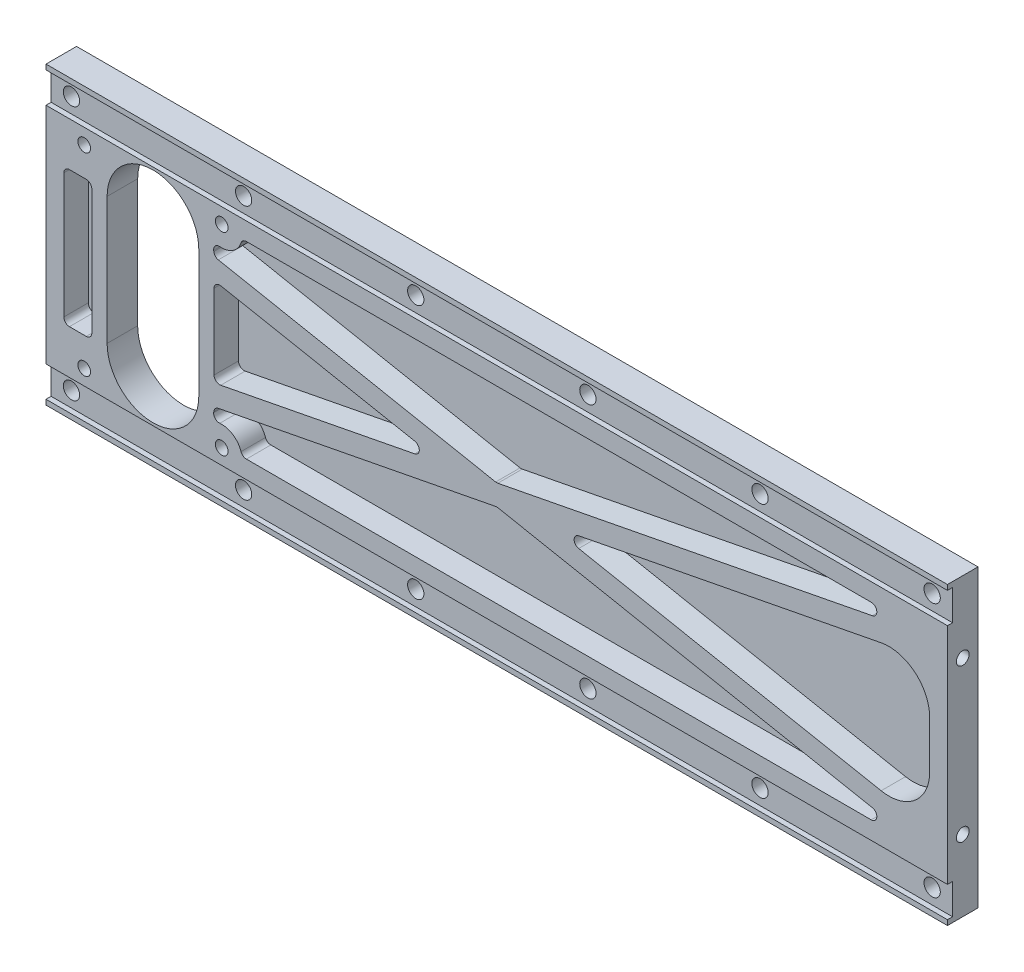
SolidWorks part; units mm, degrees
material "3.1325 (EN-AW 2017A)"
ref_plane "正面" through (0, 0, 0) normal (0, 0, 1) x (1, 0, 0)
ref_plane "平面" through (0, 0, 0) normal (0, 1, 0) x (1, 0, 0)
ref_plane "右側面" through (0, 0, 0) normal (1, 0, 0) x (0, 0, -1)
sketch "ｽｹｯﾁ1" plane through (0, 0, 0) normal (0, 0, 1) x (1, 0, 0)
  line L0 (0, 0) -> (27261.2982, 0) construction
  line L1 (0, 0) -> (0, 22) construction
  line L2 (-88.5, -29) -> (88.5, -29)
  line L3 (-88.5, -29) -> (-88.5, 29)
  line L4 (-88.5, 29) -> (88.5, 29)
  line L5 (88.5, -29) -> (88.5, 29)
  line L6 (-88.5, 28) -> (88.5, 28)
  line L7 (88.5, 22) -> (-88.5, 22)
  line L8 (-88.5, 25) -> (88.5, 25) construction
  line L9 (0, 22) -> (0, 28) construction
  line L10 (0, 28) -> (0, 29) construction
  line L11 (-88.5, -28) -> (88.5, -28)
  line L12 (88.5, -22) -> (-88.5, -22)
  line L13 (-58.5, 12.5) -> (-58.5, -12.5)
  line L14 (-76.5, -12.5) -> (-76.5, 12.5)
  line L15 (-67.5, 12.5) -> (-67.5, -12.5) construction
  arc A0 (-58.5, 12.5) -> (-76.5, 12.5) centre (-67.5, 12.5) ccw
  arc A1 (-76.5, -12.5) -> (-58.5, -12.5) centre (-67.5, -12.5) ccw
  point P9 (0, 29)
  point P10 (-88.5, 0)
  point P18 (0, 25)
  point P24 (-84.5, 25)
  point P25 (0, 15)
  point P26 (-50.7, 25)
  point P27 (-16.9, 25)
  point P28 (16.9, 25)
  point P29 (50.7, 25)
  point P30 (84.5, 25)
  point P31 (0, -15)
  point P32 (84.5, -25)
  point P33 (50.7, -25)
  point P34 (16.9, -25)
  point P35 (-16.9, -25)
  point P36 (-50.7, -25)
  point P37 (-84.5, -25)
  point P38 (-81, 19)
  point P39 (-54, 19)
  point P40 (-81, -19)
  point P41 (-54, -19)
  point P43 (-67.5, 0)
  dimension "D10" = 18
  dimension "D11" = 25
  dimension "D1" = 1
  dimension "D2" = 6
  dimension "D3" = 177
  dimension "D4" = 58
  dimension "D6" = 4
  dimension "D7" = 30
  dimension "D8" = 38
  dimension "D9" = 27
  dimension "D12" = 21
  dimension "D5" = 6
extrude "ﾎﾞｽ - 押し出し1" add sketch "ｽｹｯﾁ1" along normal mid plane 6 contours L4 L5 L2 L3
extrude "ｶｯﾄ - 押し出し1" cut sketch "ｽｹｯﾁ1<3>" against normal blind 1 from surface contours L5 L12 L3 L11 | L7 L5 L6 L3 region at (0, -25, 0) region at (0, 25, 0) starting at face at (0, 0, 3)
sketch "ｽｹｯﾁ1<3>" plane through (0, 0, 0) normal (0, 0, 1) x (1, 0, 0) same geometry as "ｽｹｯﾁ1"
extrude "ｶｯﾄ - 押し出し2" cut sketch "ｽｹｯﾁ1<4>" along normal through all both and the other way through all contours L14 A0 L13 A1
sketch "ｽｹｯﾁ1<4>" plane through (0, 0, 0) normal (0, 0, 1) x (1, 0, 0) same geometry as "ｽｹｯﾁ1"
hole_wizard "M3 すきま穴1" positions "3Dｽｹｯﾁ2" profile "ｽｹｯﾁ3" hole size "M3" standard "JIS" end condition through all
sketch3d "3Dｽｹｯﾁ2"
  point P0 (-84.5, -25, -3)
  point P2 (-50.7, -25, -3)
  point P4 (-16.9, -25, -3)
  point P6 (16.9, -25, -3)
  point P8 (50.7, -25, -3)
  point P10 (84.5, -25, -3)
  point P12 (84.5, 25, -3)
  point P14 (50.7, 25, -3)
  point P16 (16.9, 25, -3)
  point P18 (-16.9, 25, -3)
  point P20 (-50.7, 25, -3)
  point P22 (-84.5, 25, -3)
sketch "ｽｹｯﾁ3" plane through (-84.5, -25, -3) normal (1, 0, 0) x (0, 1, 0)
  line L0 (0, 0) -> (0, 6)
  line L1 (0, 6) -> (1.6, 6)
  line L2 (1.6, 6) -> (1.6, 0)
  line L5 (1.6, 0) -> (0, 0)
  line L11 (0, -6.35) -> (0, 107.95) construction
  dimension "通し穴の直径" = 3.2
  dimension "通し穴の深さ" = 6
hole_wizard "M3x0.5 ねじ穴2" positions "3Dｽｹｯﾁ4" profile "ｽｹｯﾁ5" tap size "M3x0.5" standard "JIS" end condition through all
sketch3d "3Dｽｹｯﾁ4"
  point P0 (-81, 19, 3)
  point P2 (-54, 19, -3)
  point P4 (-81, -19, 3)
  point P6 (-54, -19, 3)
sketch "ｽｹｯﾁ5" plane through (-81, 19, 3) normal (1, 0, 0) x (0, -1, 0)
  line L0 (0, 0) -> (0, 6)
  line L1 (0, 6) -> (1.25, 6)
  line L2 (1.25, 6) -> (1.25, 0)
  line L5 (1.25, 0) -> (0, 0)
  line L11 (0, -6.35) -> (0, 107.95) construction
  dimension "ねじ山の主要直径" = 2.5
  dimension "次ｻｰﾌｪｽまでのねじ下穴ﾄﾞﾘﾙの深さ" = 6
sketch "ｽｹｯﾁ6" [suppressed] plane through (0, 0, 2) normal (0, 0, 1) x (1, 0, 0)
  line L0 (-88.5, 25) -> (88.5, 25) construction
  line L1 (0, 28) -> (0, 22) construction
  line L2 (12.0135, 0) -> (0, 0) construction
  line L3 (88.5, -24.1) -> (88.5, -25.9)
  line L4 (88.5, 28) -> (-88.5, 28)
  line L5 (-88.5, 28) -> (-88.5, 22)
  line L6 (-88.5, 22) -> (88.5, 22)
  line L7 (88.5, 22) -> (88.5, 28)
  line L8 (88.5, 28) -> (-88.5, 28)
  line L9 (-88.5, 25.9) -> (-88.5, 24.1)
  line L10 (-88.5, 22) -> (88.5, 22)
  line L11 (88.5, 24.1) -> (88.5, 25.9)
  line L12 (-88.5, -22) -> (88.5, -22)
  line L13 (-88.5, -25.9) -> (-88.5, -24.1)
  line L14 (88.5, -28) -> (-88.5, -28)
  arc A0 (-88.5, 28) -> (-88.5, 25.9) centre (-88.5, 26.95) ccw
  arc A1 (-88.5, 22) -> (-88.5, 24.1) centre (-88.5, 23.05) cw
  arc A2 (88.5, 22) -> (88.5, 24.1) centre (88.5, 23.05) ccw
  arc A3 (88.5, 28) -> (88.5, 25.9) centre (88.5, 26.95) cw
  arc A4 (88.5, -28) -> (88.5, -25.9) centre (88.5, -26.95) ccw
  arc A5 (88.5, -22) -> (88.5, -24.1) centre (88.5, -23.05) cw
  arc A6 (-88.5, -22) -> (-88.5, -24.1) centre (-88.5, -23.05) ccw
  arc A7 (-88.5, -28) -> (-88.5, -25.9) centre (-88.5, -26.95) cw
  dimension "D2" = 2.1
  dimension "D1" = 0
sketch "ｽｹｯﾁ7" plane through (0, 0, 3) normal (0, 0, 1) x (1, 0, 0)
  line L4 (86.2083, 16.6969) -> (-86.2083, -16.6969) construction
  line L5 (-87.6293, 16.9721) -> (87.6293, -16.9721) construction
  line L8 (85, 18.5) -> (-85, 18.5)
  line L9 (-85, 18.5) -> (-85, -18.5)
  line L10 (-85, -18.5) -> (85, -18.5)
  line L11 (85, -18.5) -> (85, 18.5)
  line L12 (85, 18.5) -> (-85, 18.5)
  line L13 (-85, 18.5) -> (-85, -18.5)
  line L14 (-85, -18.5) -> (85, -18.5)
  line L15 (85, -18.5) -> (85, 18.5)
  line L18 (-88.0096, 15.0086) -> (87.249, -18.9356)
  line L19 (86.7191, 18.833) -> (-87.5988, -14.929)
  line L20 (-85, 18.5) -> (88.0096, -15.0086)
  line L21 (87.4525, 14.9007) -> (-85, -18.5)
  line L22 (87.0994, 16.8694) -> (-87.2185, -16.8925) construction
  line L23 (87.4797, 14.9059) -> (-86.8382, -18.856) construction
  line L24 (-87.249, 18.9356) -> (88.0096, -15.0086) construction
  dimension "D2" = 2
  dimension "D1" = 3.5
  dimension "D3" = 2
sketch "ｽｹｯﾁ10" [suppressed] plane through (0, 0, 3) normal (0, 0, 1) x (1, 0, 0)
  line L0 (86.7191, 18.833) -> (-87.5988, -14.929) construction
  line L1 (-88.0096, 15.0086) -> (87.249, -18.9356) construction
  line L2 (-85, 18.5) -> (-85, -18.5) construction
  line L3 (85, 18.5) -> (-85, 18.5) construction
  line L4 (85, -18.5) -> (85, 18.5) construction
  line L5 (-85, -18.5) -> (85, -18.5) construction
  line L6 (87.4525, 14.9007) -> (-85, -18.5) construction
  line L7 (-85, 18.5) -> (88.0096, -15.0086) construction
  line L8 (85, 18.5) -> (0, 2.0372)
  line L9 (-85, 14.4257) -> (-10.5182, 0)
  line L10 (-85, 14.4257) -> (-85, -14.4257)
  line L11 (85, 18.5) -> (-85, 18.5)
  line L12 (85, -14.4257) -> (85, 14.4257)
  line L13 (-85, -18.5) -> (85, -18.5)
  line L14 (85, 14.4257) -> (10.5182, 0)
  line L15 (-85, 18.5) -> (0, 2.0372)
  line L16 (10.5182, 0) -> (85, -14.4257)
  line L17 (0, -2.0372) -> (85, -18.5)
  line L18 (-10.5182, 0) -> (-85, -14.4257)
  line L19 (0, -2.0372) -> (-85, -18.5)
extrude "ｶｯﾄ - 押し出し4" [suppressed] cut sketch "ｽｹｯﾁ10" against normal blind 4.8
fillet "ﾌｨﾚｯﾄ2" [suppressed] radius 1.1
fillet "ﾌｨﾚｯﾄ3" [suppressed] radius 8
sketch "ｽｹｯﾁ11" plane through (0, 0, 3) normal (0, 0, 1) x (1, 0, 0)
  line L0 (86.7191, 18.833) -> (-87.5988, -14.929) construction
  line L1 (-88.0096, 15.0086) -> (87.249, -18.9356) construction
  line L2 (-85, 18.5) -> (-85, -18.5) construction
  line L3 (85, 18.5) -> (-85, 18.5) construction
  line L4 (85, -18.5) -> (85, 18.5) construction
  line L5 (-85, -18.5) -> (85, -18.5) construction
  line L6 (87.4525, 14.9007) -> (-85, -18.5) construction
  line L7 (-85, 18.5) -> (88.0096, -15.0086) construction
  line L8 (86.7191, 18.833) -> (-87.5988, -14.929)
  line L9 (-88.0096, 15.0086) -> (87.249, -18.9356)
  line L10 (-85, 18.5) -> (-85, -18.5)
  line L11 (85, 18.5) -> (-85, 18.5)
  line L12 (85, -18.5) -> (85, 18.5)
  line L13 (-85, -18.5) -> (85, -18.5)
  line L14 (87.4525, 14.9007) -> (-85, -18.5)
  line L15 (-85, 18.5) -> (88.0096, -15.0086)
  line L22 (-79.5, 12.5) -> (-79.5, -12.5)
  line L23 (-55.5, -12.5) -> (-55.5, 12.5)
  line L24 (-79.5, 12.5) -> (-79.5, -12.5)
  line L25 (-55.5, -12.5) -> (-55.5, 12.5)
  circle A3 centre (-81, 19) radius 4
  arc A5 (-79.5, -12.5) -> (-55.5, -12.5) centre (-67.5, -12.5) ccw
  arc A6 (-55.5, 12.5) -> (-79.5, 12.5) centre (-67.5, 12.5) ccw
  arc A7 (-79.5, -12.5) -> (-55.5, -12.5) centre (-67.5, -12.5) ccw
  arc A8 (-55.5, 12.5) -> (-79.5, 12.5) centre (-67.5, 12.5) ccw
  circle A9 centre (-54, 19) radius 4
  circle A10 centre (-81, -19) radius 4
  circle A11 centre (-54, -19) radius 4
  dimension "D2" = 8
  dimension "D1" = 3
sketch "ｽｹｯﾁ12" plane through (0, 0, 3) normal (0, 0, 1) x (1, 0, 0)
  line L0 (-85, 18.5) -> (88.0096, -15.0086) construction
  line L1 (87.4525, 14.9007) -> (-85, -18.5) construction
  line L2 (-79.5, 12.5) -> (-79.5, -12.5)
  line L3 (-55.5, -12.5) -> (-55.5, 12.5)
  line L4 (-85, 18.5) -> (-85, -18.5)
  line L5 (-85, -18.5) -> (85, -18.5)
  line L6 (85, -18.5) -> (85, 18.5)
  line L7 (85, 18.5) -> (-85, 18.5)
  line L8 (-85, 13.3545) -> (-85, -13.3545)
  line L9 (-50.0314, -18.5) -> (85, -18.5)
  line L10 (85, -14.4257) -> (85, 14.4257)
  line L11 (85, 18.5) -> (-50.0314, 18.5)
  line L12 (-79.5, 12.5) -> (-79.5, -12.5)
  line L13 (-55.5, -8.7121) -> (-55.5, 8.7121)
  line L14 (-88.0096, 15.0086) -> (87.249, -18.9356) construction
  line L15 (86.7191, 18.833) -> (-87.5988, -14.929) construction
  line L16 (-55.5034, 12.7871) -> (0, 2.0372)
  line L17 (85, 14.4257) -> (10.5182, 0)
  line L18 (-85, 14.4257) -> (-79.4695, 13.3545) construction
  line L19 (85, 18.5) -> (0, 2.0372)
  line L20 (-55.5, 8.7121) -> (-10.5182, 0)
  line L22 (-10.5182, 0) -> (-55.5, -8.7121)
  line L23 (0, -2.0372) -> (-55.5034, -12.7871)
  line L24 (0, -2.0372) -> (85, -18.5)
  line L25 (10.5182, 0) -> (85, -14.4257)
  line L26 (-79.4695, 13.3545) -> (-85, 13.3545)
  line L27 (0, 0) -> (-72.4986, 0) construction
  line L28 (-79.4695, -13.3545) -> (-85, -13.3545)
  arc A0 (-79.4695, 13.3545) -> (-79.5, 12.5) centre (-67.5, 12.5) ccw
  circle A1 centre (-54, 19) radius 4
  arc A2 (-55.8721, 15.4651) -> (-50.0314, 18.5) centre (-54, 19) ccw
  arc A3 (-55.8721, -15.4651) -> (-55.5034, -12.7871) centre (-67.5, -12.5) ccw
  circle A5 centre (-54, -19) radius 4
  arc A6 (-50.0314, -18.5) -> (-55.8721, -15.4651) centre (-54, -19) ccw
  arc A10 (-79.5, -12.5) -> (-55.5, -12.5) centre (-67.5, -12.5) ccw
  arc A11 (-55.5, 12.5) -> (-79.5, 12.5) centre (-67.5, 12.5) ccw
  arc A12 (-79.5, -12.5) -> (-79.4695, -13.3545) centre (-67.5, -12.5) ccw
  arc A13 (-55.5034, 12.7871) -> (-55.8721, 15.4651) centre (-67.5, 12.5) ccw
  dimension "D1" = 0
  dimension "D3" = 0
  dimension "D4" = 0
  dimension "D6" = 0
extrude "ｶｯﾄ - 押し出し5" cut sketch "ｽｹｯﾁ12" against normal blind 4.8
fillet "ﾌｨﾚｯﾄ4" radius 8 2 edges at (85, -14.4257, 0.6) (85, 14.4257, 0.6)
fillet "ﾌｨﾚｯﾄ5" radius 1.1 18 edges at (85, -18.5, 0.6) (0, -2.0372, 0.6) (-55.5034, -12.7871, 0.6) (-55.8721, -15.4651, 0.6) (-50.0314, -18.5, 0.6) (-50.0314, 18.5, 0.6) (-55.8721, 15.4651, 0.6) (-55.5034, 12.7871, 0.6) (0, 2.0372, 0.6) (85, 18.5, 0.6) (10.5182, 0, 0.6) (-55.5, -8.7121, 0.6) (-10.5182, 0, 0.6) (-55.5, 8.7121, 0.6) (-85, -13.3545, 0.6) (-79.4695, -13.3545, 0.6) (-85, 13.3545, 0.6) (-79.4695, 13.3545, 0.6)
hole_wizard "M3x0.5 ねじ穴1" positions "3Dｽｹｯﾁ3" profile "ｽｹｯﾁ4" tap size "M3x0.5" standard "JIS"
sketch3d "3Dｽｹｯﾁ3"
  point P0 (-88.5, 15, 0)
  point P4 (-88.5, -15, 0)
  point P6 (88.5, 15, 0)
  point P10 (88.5, -15, 0)
sketch "ｽｹｯﾁ4" plane through (-88.5, 15, 0) normal (0, 1, 0) x (0, 0, 1)
  line L0 (0, 0) -> (0, 9.2511)
  line L1 (0, 9.2511) -> (1.25, 8.5)
  line L2 (1.25, 8.5) -> (1.25, 0)
  line L5 (1.25, 0) -> (0, 0)
  line L10 (0, 9.2511) -> (-1.25, 8.5) construction
  line L11 (0, -6.35) -> (0, 107.95) construction
  dimension "ねじ下穴ﾄﾞﾘﾙ直径" = 2.5
  dimension "ねじ下穴ﾄﾞﾘﾙの深さ" = 8.5
  dimension "ﾄﾞﾘﾙ角度" = 118
